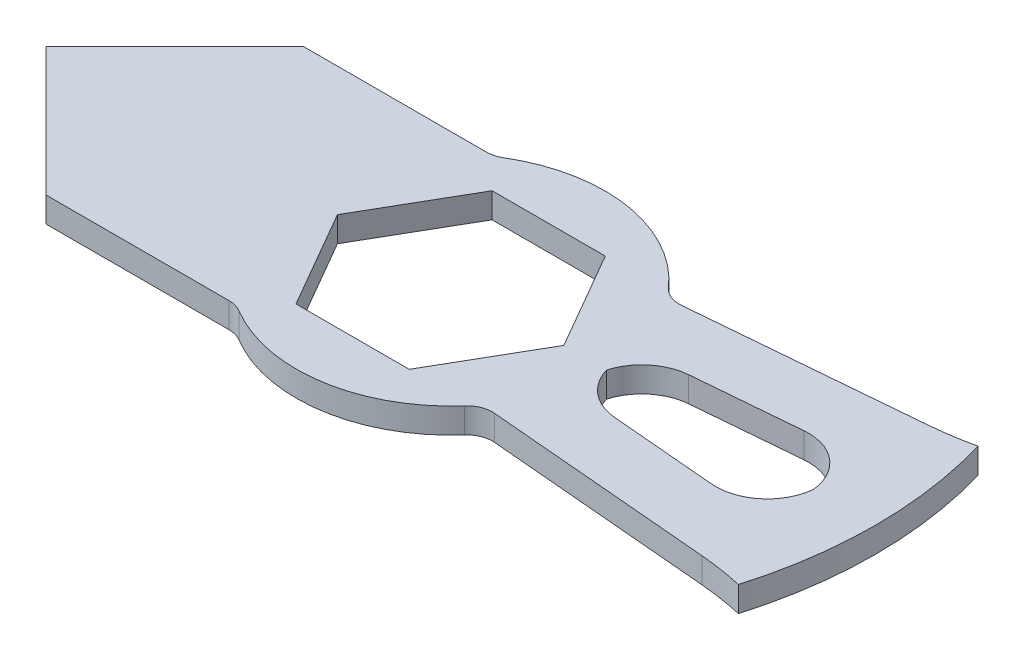
SolidWorks part; units mm, degrees
ref_plane "Front Plane" through (0, 0, 0) normal (0, 0, 1) x (1, 0, 0)
ref_plane "Top Plane" through (0, 0, 0) normal (0, 1, 0) x (1, 0, 0)
ref_plane "Right Plane" through (0, 0, 0) normal (1, 0, 0) x (0, 0, -1)
other "Center of Mass"
sketch "Sketch1" plane through (0, 0, 0) normal (0, 1, 0) x (1, 0, 0)
  line L0 (-82.55, 0) -> (82.55, 0) construction
  line L1 (0, -82.55) -> (0, 82.55) construction
  line L24 (70.7731, 21.9718) -> (24.0453, 17.9395)
  line L33 (69.8592, 9.8483) -> (29.3202, 6.3501)
  line L38 (69.8592, -9.8483) -> (29.3202, -6.3501)
  line L39 (-78.6331, 0) -> (-53.6331, 25)
  line L40 (69.8592, -9.8483) -> (17.2007, -5.3042) construction
  line L41 (69.8592, 9.8483) -> (17.2007, 5.3042) construction
  line L42 (-62.037, -13) -> (-62.037, 13) construction
  line L43 (-78.6331, 0) -> (-53.6331, -25)
  line L44 (70.7731, -21.9718) -> (24.0453, -17.9395)
  line L46 (-74.037, 25) -> (-16.5831, 25) construction
  line L47 (-74.037, -25) -> (-74.037, 25) construction
  line L48 (-74.037, -25) -> (-16.5831, -25) construction
  line L51 (-53.6331, 25) -> (-16.5831, 25)
  line L52 (-53.6331, -25) -> (-16.5831, -25)
  line L55 (-62.037, 13) -> (-12.4499, 13) construction
  line L56 (-62.037, -13) -> (-12.4499, -13) construction
  circle A0 centre (0, 0) radius 82.55 construction
  circle A6 centre (0, 0) radius 0.0381
  arc A26 (79.2, 23.278) -> (70.7731, 21.9718) centre (65.3538, 84.7726) cw
  arc A44 (69.8592, -9.8483) -> (69.8592, -9.8483) centre (69.8592, -9.8483) cw
  arc A46 (69.8592, -9.8483) -> (69.8592, 9.8483) centre (0, 0) ccw
  arc A48 (69.8592, 9.8483) -> (69.8592, 9.8483) centre (69.8592, 9.8483) ccw
  arc A49 (79.2, -23.278) -> (70.7731, -21.9718) centre (65.3538, -84.7726) ccw
  arc A51 (-12.4499, -13) -> (17.2007, -5.3042) centre (0, 0) ccw construction
  arc A56 (79.2, -23.278) -> (79.2, 23.278) centre (0, 0) ccw
  arc A59 (24.0453, 17.9395) -> (-16.5831, 25) centre (0, 0) ccw
  arc A62 (29.3202, -6.3501) -> (29.3202, 6.3501) centre (0, 0) ccw
  arc A63 (-16.5831, -25) -> (24.0453, -17.9395) centre (0, 0) ccw
  arc A65 (17.2007, 5.3042) -> (-12.4499, 13) centre (0, 0) ccw construction
  point P6 (0, 0)
  point P8 (0, 0)
  point P10 (0, 0)
  point P11 (-20.2018, 14.7271)
  point P12 (14.4373, 20.4099)
  point P13 (78.3727, 25.9271)
  point P14 (-51.1, 37.2518)
  point P16 (-51.1, -37.2518)
  point P17 (14.4373, -20.4099)
  point P18 (78.3727, -25.9271)
  point P19 (73.26, -18.4599)
  point P20 (73.26, 18.4599)
  point P21 (12.2435, 13.1946)
  point P22 (0, 0)
  point P23 (-17.5239, 4.1123)
  point P24 (-49.2137, 27.214)
  point P25 (0, 0)
  point P26 (-49.2137, -27.214)
  point P27 (-17.5239, -4.1123)
  point P28 (0, 0)
  point P29 (12.2435, -13.1946)
  point P31 (71.3749, 14.9977)
  point P32 (0, 80.1903)
  point P33 (20.4118, 10.5999)
  point P35 (80.1685, -21.4504)
  point P36 (65.5954, -84.7935)
  point P40 (-73.2494, 3.8)
  point P41 (-73.2494, -3.8)
  point P42 (-51.2614, 23)
  point P45 (-26.6376, 13.8)
  point P47 (80.1685, 21.4504)
  point P48 (-26.6376, -13.8)
  point P55 (87.0841, -25.5352)
  point P56 (71.0147, -21.9926)
  point P58 (86.8425, 25.5143)
  point P61 (-66.2494, 3.8)
  point P62 (-66.2494, -3.8)
  point P67 (-21.9718, -6.8)
  point P68 (0, 0)
  point P70 (20.4118, -10.5999)
  point P73 (71.6165, -15.0186)
  point P77 (74.4285, -15.3185)
  point P78 (0, 0)
  point P79 (74.4265, 15.3286)
  point P80 (0, 0)
  point P81 (0, 0)
  dimension "D1" = 165.1
  dimension "D2" = 30
  dimension "D5" = 0.0762
  dimension "D4" = 4.932
  dimension "D3" = 12
  dimension "D8" = 63.0342
  dimension "D7" = 25
  dimension "D9" = 46.9015
  dimension "D6" = 62.05
  dimension "D10" = 135
  dimension "D11" = 17.9395
extrude "Boss-Extrude1" add sketch "Sketch1" along normal blind 4.9 contours A49 A56 A26 L24 L44 A6 region at (-0.6914, 0, 0)
sketch "Sketch3" plane through (0, 4.9, 0) normal (0, 1, 0) x (1, 0, 0)
  line L1 (22, 0) -> (11, 19.0526)
  line L2 (11, 19.0526) -> (-11, 19.0526)
  line L3 (-11, 19.0526) -> (-22, 0)
  line L4 (-22, 0) -> (-11, -19.0526)
  line L5 (-11, -19.0526) -> (11, -19.0526)
  line L6 (11, -19.0526) -> (22, 0)
  circle A1 centre (0, 0) radius 19.0526 construction
  dimension "D1" = 22
extrude "Cut-Extrude3" cut sketch "Sketch3" against normal blind 10
fillet "Fillet4" radius 5 4 edges at (24.0453, 2.45, 17.9395) (-16.5831, 2.45, 25) (-16.5831, 2.45, -25) (24.0453, 2.45, -17.9395)
fillet "Fillet5" radius 10 4 edges at (69.8592, 2.45, 9.8483) (69.8592, 2.45, -9.8483) (29.3202, 2.45, 6.3501) (29.3202, 2.45, -6.3501)
